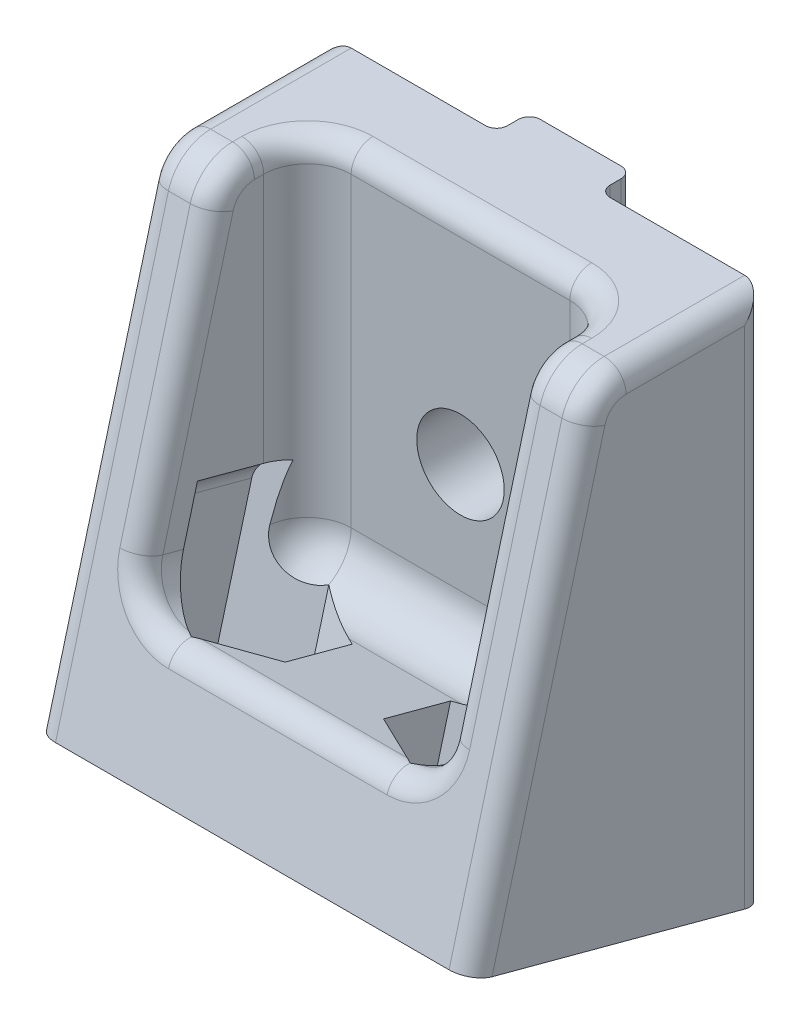
SolidWorks part; units mm, degrees
material "ABS"
ref_plane "Plan de face" through (0, 0, 0) normal (0, 0, 1) x (1, 0, 0)
ref_plane "Plan de dessus" through (0, 0, 0) normal (0, 1, 0) x (1, 0, 0)
ref_plane "Plan de droite" through (0, 0, 0) normal (1, 0, 0) x (0, 0, -1)
sketch "Esquisse1" plane through (0, 0, 0) normal (0, 1, 0) x (1, 0, 0)
  line L0 (2.35, 0) -> (10, 0)
  line L1 (-2.35, 1.5) -> (2.35, 1.5)
  line L2 (-2.35, 1.5) -> (-2.35, 0)
  line L3 (-2.35, 0) -> (2.35, 0) construction
  line L4 (2.35, 1.5) -> (2.35, 0)
  line L5 (-10, 0) -> (-2.35, 0)
  line L6 (-10, 0) -> (-10, -4)
  line L7 (-10, -4) -> (10, -4)
  line L10 (10, -4) -> (10, 0)
  dimension "D1" = 10
  dimension "D4" = 4.7
  dimension "D5" = 1.5
  dimension "D9" = 4
extrude "Boss.-Extru.1" add sketch "Esquisse1" along normal blind 10 and the other way blind 14.78
sketch "Esquisse2" plane through (-1.3724, 0, 0) normal (0, 0, 1) x (1, 0, 0)
  circle A0 centre (1.3724, 0) radius 2
  dimension "D1" = 4
extrude "Enlèv. mat.-Extru.1" cut sketch "Esquisse2" against normal through all both and the other way through all
fillet "Congé1" radius 0.5 4 edges at (2.35, -2.39, 0) (2.35, -2.39, -1.5) (-2.35, -2.39, -1.5) (-2.35, -2.39, 0)
sketch "Esquisse3" plane through (-10, 0, 0) normal (-1, 0, 0) x (0, 0, 1)
  line L0 (-1.5, -14.78) -> (4, -13.3063)
  line L1 (4, 10) -> (4, -14.78) construction
  line L2 (4, -13.3063) -> (4, -14.78)
  line L3 (4, -14.78) -> (-1.5, -14.78)
  dimension "D1" = 15
extrude "Enlèv. mat.-Extru.2" cut sketch "Esquisse3" against normal through all
sketch "Esquisse4" plane through (-10, 0, 0) normal (-1, 0, 0) x (0, 0, 1)
  line L0 (4, -13.3063) -> (0, -14.3781) construction
  line L1 (0, -14.3781) -> (13.523, -10.7546)
  line L2 (0, -14.3781) -> (0, -8.6841)
  line L3 (0, -8.6841) -> (12.0995, -5.442)
  line L4 (13.523, -10.7546) -> (12.0995, -5.442)
  dimension "D1" = 14
  dimension "D2" = 5.5
extrude "Boss.-Extru.2" add sketch "Esquisse4" against normal up to surface (20 mm away) up to face at (10, -1.9211, 2)
sketch "Esquisse5" plane through (-10, 0, 0) normal (-1, 0, 0) x (0, 0, 1)
  line L1 (0, 10) -> (0, -14.3781) construction
  line L6 (0, 10) -> (0, -14.3781)
  line L7 (0, -14.3781) -> (13.523, -10.7546)
  line L8 (13.523, -10.7546) -> (12.0995, -5.442)
  line L9 (12.0995, -5.442) -> (4, -7.6123)
  line L10 (4, -7.6123) -> (4, 10)
  line L11 (4, 10) -> (0, 10)
  line L12 (1.5, 10) -> (1.5, -13.9762)
  line L13 (1.5, -13.9762) -> (13.523, -10.7546)
  line L14 (13.523, -10.7546) -> (7.9618, 10)
  line L17 (7.9618, 10) -> (1.5, 10)
  dimension "D1" = 0
  dimension "D2" = 1.5
extrude "Boss.-Extru.3" add sketch "Esquisse5" against normal blind 3
sketch "Esquisse6" plane through (10, 0, 0) normal (1, 0, 0) x (0, 0, -1)
  line L4 (-4, -7.6123) -> (-4, 10)
  line L5 (-4, 10) -> (-7.9618, 10)
  line L6 (-4, -7.6123) -> (-4, 10)
  line L7 (-12.0995, -5.442) -> (-4, -7.6123)
  line L8 (-7.9618, 10) -> (-12.0995, -5.442)
  line L9 (-12.0995, -5.442) -> (-4, -7.6123)
  line L10 (-4, 10) -> (-7.9618, 10)
  line L13 (-7.9618, 10) -> (-12.0995, -5.442)
  dimension "D1" = 0
extrude "Boss.-Extru.4" add sketch "Esquisse6" against normal blind 3
fillet "Congé7" radius 2 7 edges at (0, -7.6123, 4) (-8.5, 10, 7.9618) (8.5, 10, 7.9618) (7, -6.5271, 8.0497) (7, 1.1939, 4) (-7, -6.5271, 8.0497) (-7, 1.1939, 4)
fillet "Congé8" radius 1 20 edges at (7, 10, 6.2136) (-10, 10, 3.2136) (-10, -1.1185, 10.941) (0, -5.442, 12.0995) (10, -1.1185, 10.941) (10, 10, 3.2136) (-7, 10, 6.2136) (10, -2.189, 0) (7, 2.5037, 9.9704) (0, 10, 4) (-7, 2.5037, 9.9704) (-10, -2.189, 0) (-6.4142, -4.8762, 11.9478) (6.4142, -4.8762, 11.9478) (7, 9.5867, 7.6446) (6.4142, 10, 4.5858) (-6.4142, 10, 4.5858) (-7, 9.5867, 7.6446) (10, 9.5867, 7.6446) (-10, 9.5867, 7.6446)
sketch "Esquisse7" plane through (0, -13.4149, 3.5945) normal (0, -0.9659, 0.2588) x (1, 0, 0)
  line L0 (0, -8.2626) -> (0, 8.2626) construction
  line L2 (-9, -3.7213) -> (-2.85, -3.7213) construction
  circle A0 centre (-5, 6.2787) radius 1.6
  circle A1 centre (5, 6.2787) radius 1.6
  dimension "D1" = 10
  dimension "D2" = 3.2
  dimension "D3" = 10
extrude "Enlèv. mat.-Extru.3" cut sketch "Esquisse7" against normal blind 3
sketch "Esquisse8" plane through (0, -10.5172, 2.8181) normal (0, -0.9659, 0.2588) x (1, 0, 0)
  line L1 (-2.25, 7.8664) -> (-5, 9.4541)
  line L2 (-5, 9.4541) -> (-7.75, 7.8664)
  line L3 (-7.75, 7.8664) -> (-7.75, 4.691)
  line L4 (-7.75, 4.691) -> (-5, 3.1033)
  line L5 (-5, 3.1033) -> (-2.25, 4.691)
  line L6 (-2.25, 4.691) -> (-2.25, 7.8664)
  line L7 (7.75, 7.8664) -> (5, 9.4541)
  line L8 (5, 9.4541) -> (2.25, 7.8664)
  line L9 (2.25, 7.8664) -> (2.25, 4.691)
  line L10 (2.25, 4.691) -> (5, 3.1033)
  line L11 (5, 3.1033) -> (7.75, 4.691)
  line L12 (7.75, 4.691) -> (7.75, 7.8664)
  circle A0 centre (-5, 6.2787) radius 2.75 construction
  circle A1 centre (5, 6.2787) radius 2.75 construction
  circle A3 centre (-5, 6.2787) radius 1.6 construction
  circle A4 centre (5, 6.2787) radius 1.6 construction
  dimension "D1" = 5.5
extrude "Enlèv. mat.-Extru.4" cut sketch "Esquisse8" against normal blind 7
fillet "Congé9" radius 1 2 edges at (-7.75, -2.1306, 7.0711) (7.75, -2.1306, 7.0711)
